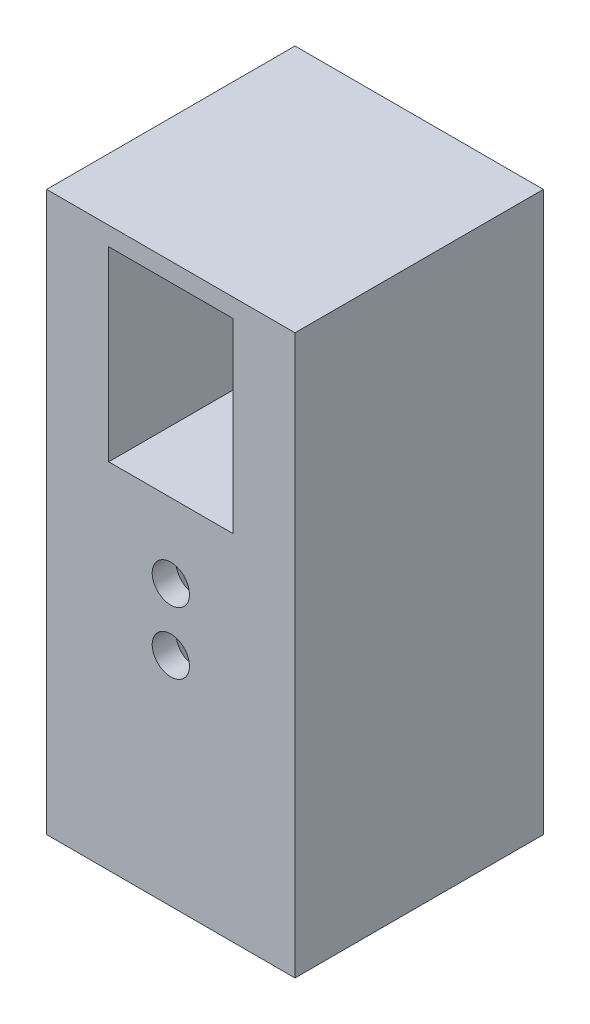
SolidWorks part; units mm, degrees
ref_plane "Front Plane" through (0, 0, 0) normal (0, 0, 1) x (1, 0, 0)
ref_plane "Top Plane" through (0, 0, 0) normal (0, 1, 0) x (1, 0, 0)
ref_plane "Right Plane" through (0, 0, 0) normal (1, 0, 0) x (0, 0, -1)
sketch "Sketch1" plane through (0, 0, 0) normal (0, 0, 1) x (1, 0, 0)
  line L0 (0, 43.5154) -> (0, -35.6563) construction
  line L1 (-41.1964, 0) -> (37.9753, 0) construction
sketch "Sketch2" plane through (0, 0, 0) normal (1, 0, 0) x (0, 0, -1)
  line L0 (41.6044, 0) -> (-41.6044, 0) construction
sketch "Sketch5" plane through (0, 0, 0) normal (0, 1, 0) x (1, 0, 0)
  line L0 (74.93, 25.6173) -> (95.25, 25.6173)
  line L1 (0, 101.6) -> (101.6, 101.6)
  line L2 (0, 101.6) -> (0, 0)
  line L3 (0, 0) -> (101.6, 0)
  line L4 (101.6, 101.6) -> (101.6, 0)
  line L5 (6.35, 25.6173) -> (26.67, 25.6173)
  line L6 (6.35, 25.6173) -> (6.35, 5.2973)
  line L7 (6.35, 5.2973) -> (26.67, 5.2973)
  line L8 (26.67, 25.6173) -> (26.67, 5.2973)
  line L9 (74.93, 25.6173) -> (74.93, 5.2973)
  line L10 (74.93, 5.2973) -> (95.25, 5.2973)
  line L11 (95.25, 25.6173) -> (95.25, 5.2973)
  line L12 (74.93, 95.25) -> (95.25, 95.25)
  line L13 (74.93, 95.25) -> (74.93, 74.93)
  line L14 (74.93, 74.93) -> (95.25, 74.93)
  line L15 (95.25, 95.25) -> (95.25, 74.93)
  line L16 (6.35, 95.25) -> (26.67, 95.25)
  line L17 (6.35, 95.25) -> (6.35, 74.93)
  line L18 (6.35, 74.93) -> (26.67, 74.93)
  line L19 (26.67, 95.25) -> (26.67, 74.93)
  dimension "D1" = 101.6
  dimension "D2" = 101.6
  dimension "D3" = 20.32
  dimension "D4" = 20.32
  dimension "D5" = 6.35
  dimension "D6" = 5.2973
  dimension "D9" = 6.35
  dimension "D10" = 6.35
  dimension "D11" = 6.35
  dimension "D7" = 2
  dimension "D8" = 2
extrude "Boss-Extrude1" add sketch "Sketch5" along normal blind 228.6 contours L4 L1 L2 L3 L5 L8 L7 L6 L0 L11 L10 L9 L12 L15 L14 L13 L16 L19 L18 L17 | L11 L0 L9 L10 | L15 L12 L13 L14 | L8 L5 L6 L7 | L19 L16 L17 L18 region at (85.09, 0, -15.4573) region at (50.8, 0, -50.9003) region at (16.51, 0, -15.4573) region at (85.09, 0, -85.09) region at (16.51, 0, -85.09)
sketch "Sketch6" plane through (0, 0, 0) normal (0, 1, 0) x (1, 0, 0)
  circle A0 centre (50.8, 50.8) radius 41.91
  point P2 (0, 0)
  dimension "D1" = 83.82
  dimension "D2" = 50.8
  dimension "D3" = 50.8
extrude "Cut-Extrude1" cut sketch "Sketch6" along normal blind 127 contours A0
extrude "Cut-Extrude2" cut sketch "Sketch5<3>" along normal blind 25.4 contours L8 L5 L6 L7 | L11 L0 L9 L10 | L15 L12 L13 L14 | L19 L16 L17 L18 region at (85.09, 0, -15.4573) region at (16.51, 0, -15.4573) region at (85.09, 0, -85.09) region at (16.51, 0, -85.09)
sketch "Sketch5<3>" plane through (0, 0, 0) normal (0, 1, 0) x (1, 0, 0) same geometry as "Sketch5"
sketch3d "3DSketch2" plane through (0, 0, 0) normal (0, 0, 1) x (1, 0, 0)
  dimension "D1" = 7.62
sketch "Sketch7" plane through (0, 220.98, 0) normal (0, 1, 0) x (1, 0, 0)
  line L3 (76.2, 50.8) -> (76.2, -137.2968)
  line L4 (76.2, -137.2968) -> (25.4, -137.2968)
  line L5 (25.4, 50.8) -> (25.4, -137.2968)
  arc A0 (76.2, 50.8) -> (25.4, 50.8) centre (50.8, 50.8) ccw
  dimension "D1" = 25.4
  dimension "D2" = 50.8
  dimension "D3" = 50.8
extrude "Cut-Extrude3" cut sketch "Sketch7" against normal blind 76.2
sketch "Sketch9" plane through (0, 0, 0) normal (0, 0, 1) x (1, 0, 0)
  circle A0 centre (50.8, 114.3) radius 7.62
  circle A1 centre (50.8, 88.9) radius 7.62
  dimension "D1" = 15.24
  dimension "D2" = 50.8
  dimension "D3" = 114.3
  dimension "D4" = 2
extrude "Cut-Extrude4" cut sketch "Sketch9" against normal blind 56.642
